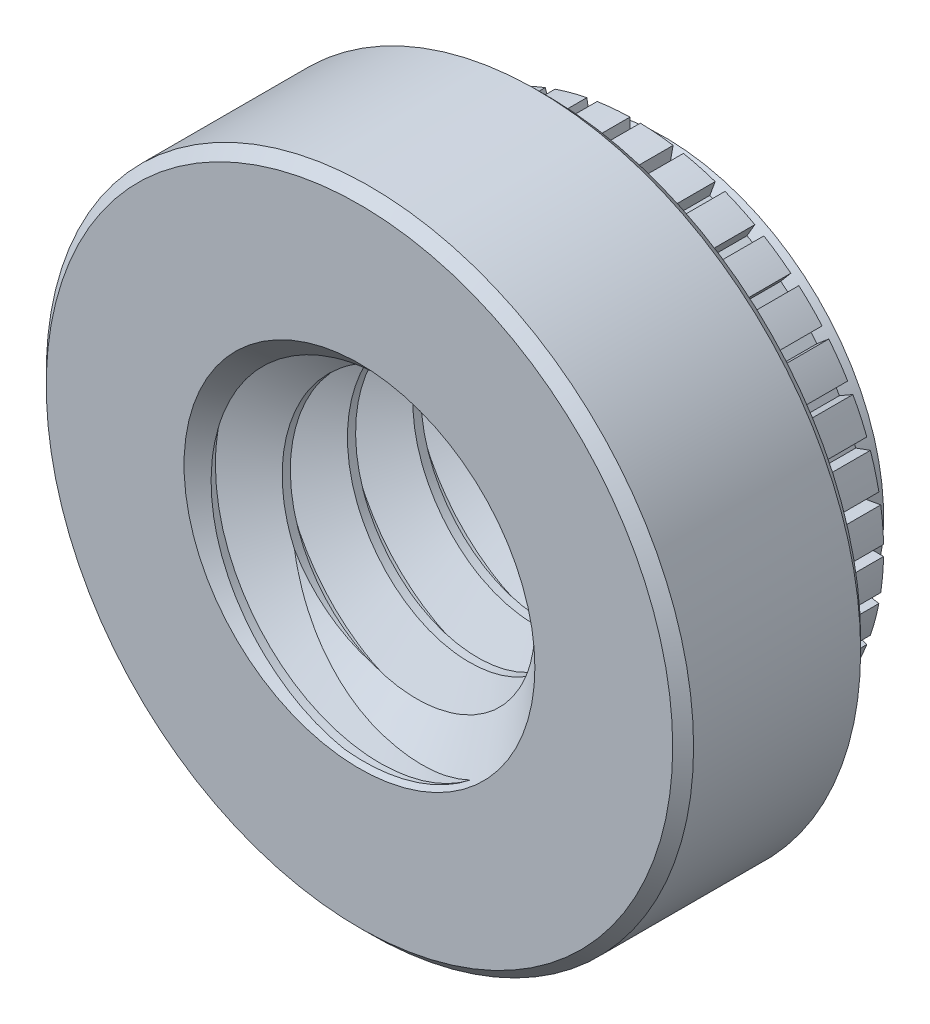
SolidWorks part; units mm, degrees
ref_plane "Front Plane" through (0, 0, 0) normal (0, 0, 1) x (1, 0, 0)
ref_plane "Top Plane" through (0, 0, 0) normal (0, 1, 0) x (1, 0, 0)
ref_plane "Right Plane" through (0, 0, 0) normal (1, 0, 0) x (0, 0, -1)
sketch "Sketch1" plane through (0, 0, 0) normal (0, 0, 1) x (1, 0, 0)
  circle A0 centre (0, 0) radius 3.937
  dimension "A" = 7.874
extrude "Extrude1" add sketch "Sketch1" against normal blind 2.286
sketch "Sketch15" plane through (0, 0, -2.286) normal (0, 0, -1) x (-1, 0, 0)
  circle A0 centre (0, 0) radius 2.7051
  dimension "hole dia" = 5.4102
sketch "Sketch2" plane through (0, 0, -2.286) normal (0, 0, -1) x (-1, 0, 0)
  circle A0 centre (0, 0) radius 3.0226
  dimension "D1" = 6.0452
extrude "Extrude2" add sketch "Sketch2" along normal blind 1.4224
sketch "Sketch3" plane through (0, 0, -3.7084) normal (0, 0, -1) x (-1, 0, 0)
  line L0 (0, 2.8321) -> (0, 3.937)
  circle A1 centre (0, 0) radius 3.937 construction
  circle A2 centre (0, 0) radius 2.8321
  circle A3 centre (0, 0) radius 2.8321 construction
  dimension "D1" = 0.1905
extrude "Cut-Extrude-Thin1" cut sketch "Sketch3" against normal up to surface (1.4224 mm away) thin up to face at (3.937, 0, -2.286) thin type mid plane wall 0.127
pattern_circular "CirPattern1" count 36 over 360 about axis through (0, 0, 0) along (0, 0, 1) of "Cut-Extrude-Thin1"
sketch "Sketch5" plane through (0, 0, -3.7084) normal (0, 0, -1) x (-1, 0, 0)
  circle A0 centre (0, 0) radius 3.937 construction
  circle A3 centre (0, 0) radius 2.667
  dimension "C" = 5.334
extrude "Cut-Extrude1" cut sketch "Sketch5" against normal blind 0.3556 draft 20 flip side to cut draft outward yes
chamfer "Chamfer2" distance 0.127 angle 45 2 edges at (3.937, 0, 0) (3.937, 0, -2.286)
sketch "Sketch7" plane through (0, 0, 0) normal (0, 0, 1) x (1, 0, 0)
  circle A0 centre (0, 0) radius 2.0828
  dimension "Thread Od" = 4.1656
extrude "Cut-Extrude3" cut sketch "Sketch7" against normal through all
sketch "Sketch8" plane through (0, 0, -3.7084) normal (0, 0, -1) x (-1, 0, 0)
  circle A0 centre (0, 0) radius 2.0828 construction
  circle A1 centre (0, 0) radius 2.0828
curve "Helix/Spiral1" pitch 0.7937 height 6.8834 turns 8.672 parameters "pitch"=0.7937
sketch "Sketch9" plane through (0, 0, 0) normal (1, 0, 0) x (0, 0, -1)
  line L0 (4.4029, 2.0828) -> (4.1053, 1.5672)
  line L1 (4.1053, 1.5672) -> (4.0061, 1.5672)
  line L2 (4.0061, 1.5672) -> (3.7084, 2.0828)
  line L3 (4.4029, 2.0828) -> (3.7084, 2.0828)
  line L4 (4.0557, 2.0828) -> (4.0557, 1.5672) construction
  line L5 (4.2541, 1.825) -> (3.8572, 1.825) construction
  line L6 (3.7084, -2.0828) -> (3.7084, 2.0828) construction
  dimension "D1" = 60
  dimension "D2" = 0.0992
  dimension "D3" = 0.3969
sweep "Sweep1" add profiles "Sketch9" path "Helix/Spiral1"
sketch "Sketch10" plane through (0, 0, 0) normal (0, 0, 1) x (1, 0, 0)
  circle A0 centre (0, 0) radius 3.937 construction
  circle A1 centre (0, 0) radius 3.937
extrude "Cut-Extrude4" cut sketch "Sketch10" along normal through all
sketch "Sketch11" plane through (0, 0, -3.7084) normal (0, 0, -1) x (-1, 0, 0)
  circle A1 centre (0, 0) radius 2.667 construction
  circle A2 centre (0, 0) radius 2.667
extrude "Cut-Extrude5" cut sketch "Sketch11" along normal through all
sketch "Sketch13" plane through (0, 0, 0) normal (0, 0, 1) x (1, 0, 0)
  circle A2 centre (0, 0) radius 2.1336
  circle A3 centre (0, 0) radius 2.1336
  dimension "D1" = 0.0508
extrude "Cut-Extrude6" cut sketch "Sketch13" against normal through all draft 45
sketch "Sketch14" plane through (0, 0, -3.7084) normal (0, 0, -1) x (-1, 0, 0)
  circle A2 centre (0, 0) radius 2.1336
  circle A3 centre (0, 0) radius 2.1336
  dimension "D1" = 0.0508
extrude "Cut-Extrude7" cut sketch "Sketch14" against normal through all draft 45
equation "\"D3@Helix/Spiral1\" = \"B@Extrude1\"+\"panel min.@Extrude2\"+.125"
equation "\"D2@Sketch9\" = \"pitch@Helix/Spiral1\"*.125"
equation "\"D3@Sketch9\" = \"pitch@Helix/Spiral1\"*.50"
equation "\"D1@Sketch2\" = \"hole dia@Sketch15\"+.025"
equation "\"D1@Cut-Extrude1\" = \"panel min.@Extrude2\"*.25"
